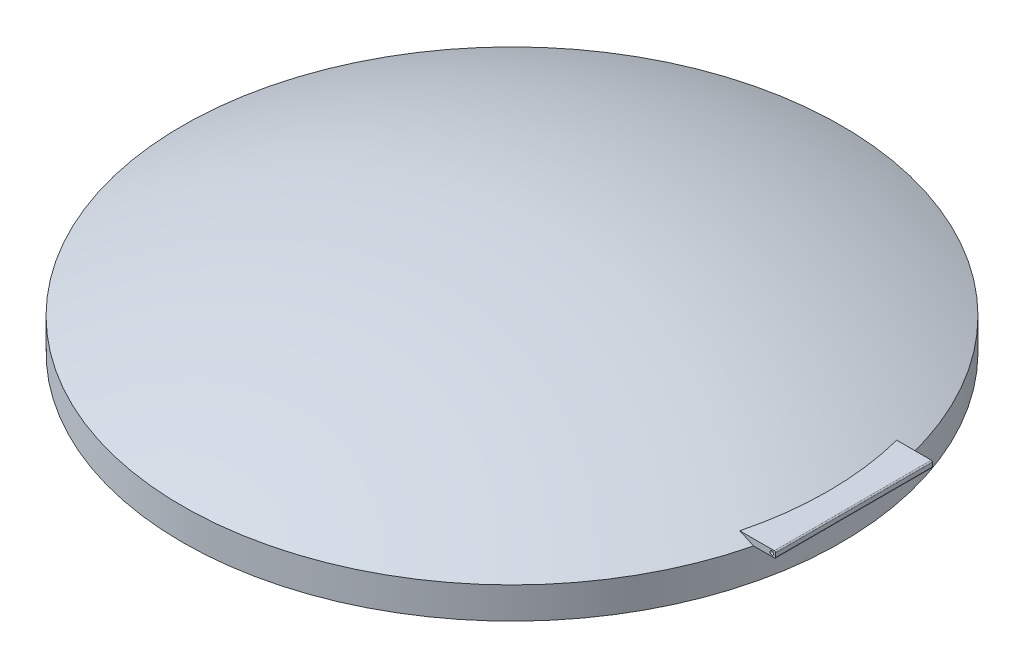
SolidWorks part; units mm, degrees
ref_plane "Front Plane" through (0, 0, 0) normal (0, 0, 1) x (1, 0, 0)
ref_plane "Top Plane" through (0, 0, 0) normal (0, 1, 0) x (1, 0, 0)
ref_plane "Right Plane" through (0, 0, 0) normal (1, 0, 0) x (0, 0, -1)
sketch "Sketch1" plane through (0, 0, 0) normal (0, 1, 0) x (1, 0, 0)
  circle A0 centre (0, 0) radius 2.625
  dimension "D1" = 5.25
extrude "Boss-Extrude1" add sketch "Sketch1" along normal blind 0.25
dome "Dome1" faces to dome 1 distance 0.6 reverse direction no elliptical dome no face at (0, 0.25, 2.625) parameters "D1"=0.6
shell "Shell1" thickness 0.1 removed face at (0, 0, 2.625)
ref_plane "Plane1" through (2.625, 0, 0) normal (1, 0, 0) x (0, 0, -1)
sketch "Sketch2" plane through (2.625, 0, 0) normal (1, 0, 0) x (0, 0, -1)
  line L0 (-0.625, 0.25) -> (0.625, 0.25)
  line L1 (-2.625, 0.25) -> (2.625, 0.25) construction
  line L2 (0.625, 0.25) -> (0.625, 0.3)
  line L3 (0.625, 0.3) -> (-0.625, 0.3)
  line L4 (-0.625, 0.3) -> (-0.625, 0.25)
  point P4 (0, 0.25)
  dimension "D1" = 1.25
  dimension "D2" = 0.05
extrude "Boss-Extrude2" add sketch "Sketch2" along normal blind 0.1 and the other way up to body
fillet "Fillet1" radius 0.01 2 edges at (2.725, 0.25, 0) (2.725, 0.3, 0)
sketch "Sketch3" plane through (0, 0, 0.625) normal (0, 0, 1) x (1, 0, 0)
  line L0 (2.725, 0.29) -> (2.725, 0.26) construction
  line L1 (2.4399, 0.3) -> (2.715, 0.3) construction
  circle A0 centre (2.695, 0.275) radius 0.015
  point P5 (2.725, 0.275)
  dimension "D2" = 0.03
  dimension "D1" = 0.03
  dimension "D3" = 0.025
extrude "Cut-Extrude1" cut sketch "Sketch3" against normal up to next
